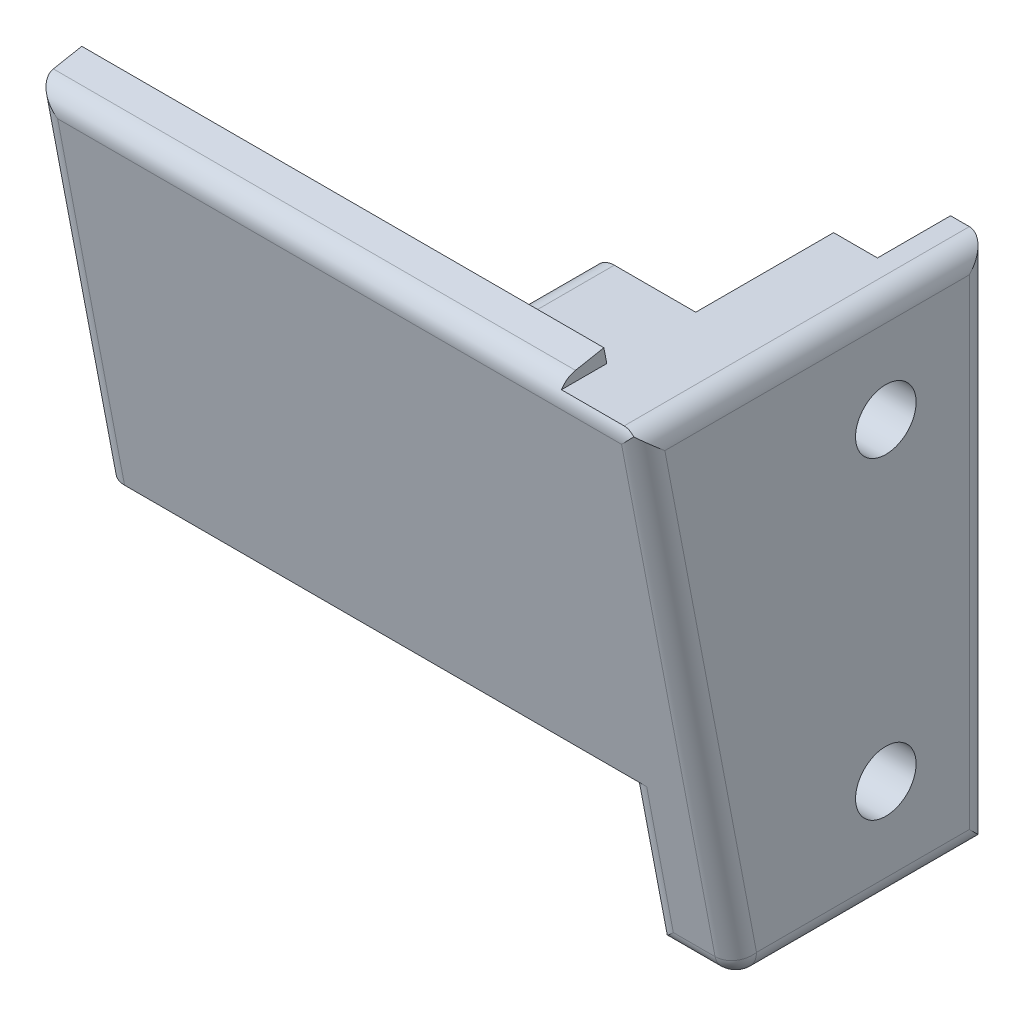
SolidWorks part; units mm, degrees
ref_plane "前视基准面" through (0, 0, 0) normal (0, 0, 1) x (1, 0, 0)
ref_plane "上视基准面" through (0, 0, 0) normal (0, 1, 0) x (1, 0, 0)
ref_plane "右视基准面" through (0, 0, 0) normal (1, 0, 0) x (0, 0, -1)
other "Configuration Table"
sketch "草图1" plane through (0, 0, 0) normal (1, 0, 0) x (0, 0, -1)
  line L0 (0, 0) -> (-10, 0)
  line L1 (-10, 0) -> (-17.6299, 40)
  line L2 (-17.6299, 40) -> (-10, 41.4554)
  line L3 (-10, 41.4554) -> (-4, 10)
  line L4 (-4, 10) -> (0, 10)
  line L5 (0, 10) -> (0, 0)
  dimension "D1" = 10
  dimension "D2" = 4
  dimension "D3" = 10
  dimension "D4" = 6
  dimension "D5" = 40
extrude "凸台-拉伸1" add sketch "草图1" along normal blind 50
sketch "草图2" plane through (0, 0, 0) normal (0, -1, 0) x (1, 0, 0)
  line L4 (0, 10) -> (0, 0)
  line L5 (0, 0) -> (50, 0)
  line L6 (50, 0) -> (50, 10)
  line L7 (50, 10) -> (0, 10)
  line L8 (0, 10) -> (0, 0)
  line L9 (0, 0) -> (50, 0)
  line L10 (50, 0) -> (50, 10)
  line L11 (50, 10) -> (0, 10)
  dimension "D1" = 0
extrude "凸台-拉伸2" add sketch "草图2" along normal blind 10
sketch "草图3" plane through (0, 0, 0) normal (-1, 0, 0) x (0, 0, 1)
  line L1 (0, 10) -> (10, 10)
  line L2 (0, 10) -> (0, -10)
  line L3 (0, -10) -> (10, -10)
  line L4 (10, 10) -> (10, -10)
extrude "凸台-拉伸3" add sketch "草图3" along normal blind 20
sketch "草图4" plane through (0, 10, 0) normal (0, 1, 0) x (1, 0, 0)
  line L1 (-20, 0) -> (0, 0)
  line L2 (-20, 0) -> (-20, -10)
  line L3 (-20, -10) -> (0, -10)
  line L4 (0, 0) -> (0, -10)
extrude "凸台-拉伸4" add sketch "草图4" along normal blind 30
sketch "草图5" plane through (50, 0, 0) normal (1, 0, 0) x (0, 0, -1)
  line L0 (-10, 10.004) -> (-11.9082, 10.004)
  line L1 (-17.6299, 40) -> (-10, 0) construction
  line L2 (-11.9082, 10.004) -> (-10, 0)
  line L3 (-10, 0) -> (-10, 10.004)
extrude "切除-拉伸1" cut sketch "草图5" against normal up to surface (50 mm away) up to face at (0, 32.2911, 11.4705)
chamfer "倒角1" distance 2 angle 45 1 edges at (25, 10.004, 10)
sketch "草图9" plane through (0, 0, 10) normal (0, 0, 1) x (1, 0, 0)
  line L0 (-20, 40) -> (-10, 40) construction
  line L1 (-20, 40) -> (0, 40) construction
  line L2 (-10, 40) -> (-10, 30) construction
  line L3 (50, -10) -> (50, 0) construction
  line L4 (50, -10) -> (50, 8.004) construction
  line L5 (50, 0) -> (-10, 0) construction
  line L6 (-20, -10) -> (-20, 40) construction
  circle A0 centre (-10, 30) radius 1.5
  circle A1 centre (-10, 0) radius 1.5
  dimension "D3" = 3
  dimension "D5" = 3
  dimension "D4" = 10
  dimension "D1" = 10
  dimension "D2" = 10
extrude "切除-拉伸2" cut sketch "草图9" against normal through all
sketch "草图12" plane through (0, 0, 10) normal (0, 0, 1) x (1, 0, 0)
  line L8 (0, 40) -> (-20, 40)
  line L9 (50, -10) -> (50, 8.004)
  line L10 (50, 8.004) -> (0, 8.004)
  line L11 (0, 8.004) -> (0, 40)
  line L15 (50, -10) -> (50, 8.004)
  line L16 (50, 8.004) -> (0, 8.004)
  line L17 (0, 8.004) -> (0, 40)
  line L19 (0, 40) -> (-20, 40)
  line L20 (-20, 40) -> (-20, -10)
  line L21 (-20, 40) -> (-20, -10)
  line L22 (-20, -10) -> (50, -10)
  line L23 (-20, -10) -> (50, -10)
  dimension "D1" = 0
extrude "切除-拉伸4" cut sketch "草图12" against normal blind 6
sketch "草图13" plane through (0, 8.004, 0) normal (0, -1, 0) x (1, 0, 0)
  line L0 (50, 4) -> (0, 4) construction
  line L1 (0, 10) -> (4, 10)
  line L2 (0, 10) -> (0, 4)
  line L3 (0, 4) -> (4, 4)
  line L4 (4, 10) -> (4, 4)
  line L6 (50, 10) -> (46, 10)
  line L7 (50, 10) -> (50, 4)
  line L8 (50, 4) -> (46, 4)
  line L9 (46, 10) -> (46, 4)
  dimension "D1" = 4
  dimension "D2" = 4
extrude "凸台-拉伸12" add sketch "草图13" along normal up to surface (18.004 mm away) up to face at (15, -10, 2)
sketch "草图15" plane through (0, 0, 0) normal (0, 0, -1) x (-1, 0, 0)
  line L0 (-25, 10) -> (-25, 20.01) construction
  line L1 (0, 40) -> (20, 40) construction
  line L2 (0, 40) -> (0, -10) construction
  line L3 (0, -10) -> (20, -10) construction
  line L4 (20, 40) -> (20, -10) construction
  line L5 (-50, 10) -> (0, 10) construction
  line L6 (-50, -10) -> (-70, -10)
  line L7 (-70, 40) -> (-70, -10)
  line L8 (-50, 40) -> (-70, 40)
  line L9 (-50, 40) -> (-50, -10)
  circle A0 centre (10, 30) radius 1.5 construction
  circle A1 centre (-60, 30) radius 1.5
extrude "凸台-拉伸14" add sketch "草图15" against normal up to surface (4 mm away) up to face at (-8.5, 30, 4)
sketch "草图16" plane through (0, 0, 4) normal (0, 0, 1) x (1, 0, 0)
  line L5 (-20, -10) -> (0, -10)
  line L6 (0, -10) -> (0, 10)
  line L7 (0, 10) -> (0, 40)
  line L8 (0, 40) -> (-20, 40)
  line L9 (-20, 40) -> (-20, -10)
  line L10 (-20, -10) -> (0, -10)
  line L11 (0, -10) -> (0, 10)
  line L12 (0, 10) -> (0, 40)
  line L13 (0, 40) -> (-20, 40)
  line L14 (-20, 40) -> (-20, -10)
  dimension "D1" = 0
extrude "切除-拉伸5" cut sketch "草图16" against normal up to surface (4 mm away) up to face at (-8.5, 30, 0)
sketch "草图17" plane through (0, 0, 4) normal (0, 0, 1) x (1, 0, 0)
  line L1 (50, 10) -> (70, 10)
  line L2 (50, 10) -> (50, -10)
  line L3 (50, -10) -> (70, -10)
  line L4 (70, 10) -> (70, -10)
extrude "凸台-拉伸15" add sketch "草图17" along normal up to surface (6 mm away) up to face at (48, -0.998, 10)
sketch "草图18" plane through (0, 10, 0) normal (0, 1, 0) x (1, 0, 0)
  line L1 (0, 0) -> (50, 0)
  line L2 (0, 0) -> (0, -4)
  line L3 (0, -4) -> (50, -4)
  line L4 (50, 0) -> (50, -4)
extrude "切除-拉伸6" cut sketch "草图18" against normal up to surface (20 mm away) up to face at (30, -10, 6)
sketch "草图19" plane through (0, -10, 0) normal (0, -1, 0) x (1, 0, 0)
  line L1 (50, 6) -> (46, 6)
  line L2 (50, 6) -> (50, 10)
  line L3 (50, 10) -> (46, 10)
  line L4 (46, 6) -> (46, 10)
  line L5 (4, 6) -> (0, 6)
  line L6 (4, 6) -> (4, 10)
  line L7 (4, 10) -> (0, 10)
  line L8 (0, 6) -> (0, 10)
extrude "切除-拉伸9" cut sketch "草图19" against normal up to surface (18.004 mm away) up to face at (25, 8.004, 7)
sketch "草图20" plane through (0, 0, 4) normal (0, 0, 1) x (1, 0, 0)
  line L0 (50, 10) -> (70, 10) construction
  line L1 (50, 40) -> (55, 40)
  line L2 (50, 40) -> (50, 10)
  line L3 (50, 10) -> (55, 10)
  line L4 (55, 40) -> (55, 10)
  dimension "D1" = 5
extrude "凸台-拉伸16" add sketch "草图20" along normal up to surface (13.6299 mm away)
sketch "草图21" plane through (0, 8.004, 0) normal (0, -1, 0) x (1, 0, 0)
  line L4 (50, 10) -> (0, 10)
  line L5 (0, 10) -> (0, 6)
  line L6 (4, 4) -> (46, 4)
  line L8 (50, 10) -> (0, 10)
  line L10 (4, 4) -> (46, 4)
  line L12 (0, 10) -> (0, 6)
  line L14 (50, 6) -> (50, 10)
  line L15 (50, 6) -> (50, 10)
  line L20 (4, 6) -> (4, 4)
  line L21 (4, 6) -> (4, 4)
  line L22 (46, 4) -> (46, 6)
  line L23 (46, 4) -> (46, 6)
  line L24 (46, 6) -> (50, 6)
  line L25 (46, 6) -> (50, 6)
  line L26 (0, 6) -> (4, 6)
  line L27 (0, 6) -> (4, 6)
  dimension "D1" = 0
extrude "凸台-拉伸17" add sketch "草图21" along normal up to surface (18.004 mm away) up to face at (54, -10, 5)
sketch "草图22" plane through (0, 0, 10) normal (0, 0, 1) x (1, 0, 0)
  line L0 (70, 10) -> (70, -10) construction
  line L1 (10, 5) -> (70, 5)
  line L2 (10, 5) -> (10, -5)
  line L3 (10, -5) -> (70, -5)
  line L4 (70, 5) -> (70, -5)
  line L5 (55, 10) -> (70, 10) construction
  line L6 (70, -10) -> (0, -10) construction
  line L8 (0, -10) -> (0, 8.004) construction
  dimension "D1" = 5
  dimension "D2" = 5
  dimension "D3" = 10
extrude "切除-拉伸10" cut sketch "草图22" against normal up to surface (6 mm away) up to face at (61.5, 30, 4)
sketch "草图23" plane through (0, 0, 0) normal (0, 0, -1) x (-1, 0, 0)
  line L0 (-60, 30) -> (-60, 0) construction
  circle A0 centre (-60, 0) radius 1.5
  dimension "D1" = 3
extrude "切除-拉伸11" cut sketch "草图23" against normal up to surface (4 mm away) up to face at (60, 0, 4)
chamfer "倒角2" distance 1 angle 45 1 edges at (52.5, 10, 10)
sketch "草图24" plane through (0, 0, 4) normal (0, 0, 1) x (1, 0, 0)
  circle A0 centre (60, 30) radius 3
  circle A1 centre (60, 0) radius 3
  dimension "D1" = 6
  dimension "D2" = 6
extrude "切除-拉伸12" cut sketch "草图24" against normal blind 2
sketch "草图25" plane through (0, 0, 10) normal (0, 0, 1) x (1, 0, 0)
  line L1 (55, 40) -> (70, 40)
  line L2 (55, 40) -> (55, -10)
  line L3 (55, -10) -> (70, -10)
  line L4 (70, 40) -> (70, -10)
extrude "切除-拉伸13" cut sketch "草图25" against normal up to surface (10 mm away) up to face at (58.5, 0, 0)
sketch "草图26" plane through (0, 0, 0) normal (0, 0, -1) x (-1, 0, 0)
  line L4 (-50, 40) -> (-55, 40)
  line L5 (-55, 40) -> (-55, -10)
  line L6 (-55, -10) -> (-50, -10)
  line L7 (-50, -10) -> (-50, 40)
  line L8 (-50, 40) -> (-55, 40)
  line L9 (-55, 40) -> (-55, -10)
  line L10 (-55, -10) -> (-50, -10)
  line L11 (-50, -10) -> (-50, 40)
  dimension "D1" = 0
extrude "凸台-拉伸18" add sketch "草图26" along normal blind 19
sketch "草图27" plane through (50, 0, 0) normal (-1, 0, 0) x (0, 0, 1)
  line L0 (4, -10) -> (-19, -10) construction
  line L1 (-19, 40) -> (-12, 40)
  line L2 (-19, 40) -> (-19, -10)
  line L3 (-19, -10) -> (-12, -10)
  line L4 (-12, 40) -> (-12, -10)
  dimension "D1" = 7
extrude "切除-拉伸14" cut sketch "草图27" against normal blind 4.2
sketch "草图28" plane through (55, 0, 0) normal (1, 0, 0) x (0, 0, -1)
  line L10 (-10, -10) -> (19, -10)
  line L11 (19, -10) -> (19, 40)
  line L12 (19, 40) -> (-17.6299, 40)
  line L13 (-17.6299, 40) -> (-11.9075, 10)
  line L14 (-11.9075, 10) -> (-11, 10)
  line L15 (-10, 9) -> (-10, 5)
  line L16 (-10, 5) -> (-4, 5)
  line L17 (-4, 5) -> (-4, -5)
  line L18 (-4, -5) -> (-10, -5)
  line L19 (-10, -5) -> (-10, -10)
  line L20 (-10, -10) -> (19, -10)
  line L21 (19, -10) -> (19, 40)
  line L22 (19, 40) -> (-17.6299, 40)
  line L23 (-17.6299, 40) -> (-11.9075, 10)
  line L25 (-10, 9) -> (-10, 5)
  line L26 (-10, 5) -> (-4, 5)
  line L27 (-4, 5) -> (-4, -5)
  line L28 (-4, -5) -> (-10, -5)
  line L29 (-10, -5) -> (-10, -10)
  line L30 (-11.9075, 10) -> (-11, 10)
  line L32 (-11, 10) -> (-10, 9)
  line L33 (-11, 10) -> (-10, 9)
  dimension "D1" = 0
extrude "凸台-拉伸19" add sketch "草图28" along normal blind 3
sketch "草图29" plane through (58, 0, 0) normal (1, 0, 0) x (0, 0, -1)
  line L0 (19, 40) -> (9, 40) construction
  line L1 (19, 40) -> (-17.6299, 40) construction
  line L2 (9, 40) -> (9, 30) construction
  line L3 (9, 30) -> (9, 0) construction
  circle A0 centre (9, 30) radius 1.5
  circle A1 centre (9, 0) radius 1.5
  dimension "D4" = 3
  dimension "D5" = 3
  dimension "D1" = 10
  dimension "D2" = 10
  dimension "D3" = 30
extrude "切除-拉伸15" cut sketch "草图29" against normal blind 13
sketch "草图30" plane through (58, 0, 0) normal (1, 0, 0) x (0, 0, -1)
  circle A0 centre (9, 30) radius 2.9
  circle A1 centre (9, 0) radius 2.9
  dimension "D1" = 5.8
  dimension "D2" = 5.8
extrude "切除-拉伸16" cut sketch "草图30" against normal offset from surface (6 mm away) 2 up to face at (50, 40.4851, 12.4508)
sketch "草图31" plane through (10, 0, 0) normal (1, 0, 0) x (0, 0, -1)
  line L4 (-4, 5) -> (-10, 5)
  line L5 (-10, 5) -> (-10, -5)
  line L6 (-10, -5) -> (-4, -5)
  line L7 (-4, -5) -> (-4, 5)
  line L8 (-4, 5) -> (-10, 5)
  line L9 (-10, 5) -> (-10, -5)
  line L10 (-10, -5) -> (-4, -5)
  line L11 (-4, -5) -> (-4, 5)
  dimension "D1" = 0
extrude "切除-拉伸17" cut sketch "草图31" against normal up to surface (10 mm away) up to face at (0, 12.7643, 9.6452)
sketch "草图32" plane through (0, 0, 4) normal (0, 0, 1) x (1, 0, 0)
  line L4 (50, -5) -> (58, -5)
  line L5 (58, -5) -> (58, 5)
  line L6 (58, 5) -> (50, 5)
  line L7 (50, 5) -> (50, -5)
  line L8 (50, -5) -> (58, -5)
  line L9 (58, -5) -> (58, 5)
  line L10 (58, 5) -> (50, 5)
  line L11 (50, 5) -> (50, -5)
  dimension "D1" = 0
extrude "凸台-拉伸20" add sketch "草图32" along normal up to surface (6 mm away) up to face at (36, 7.3347, 10)
sketch "草图33" plane through (0, 0, 10) normal (0, 0, 1) x (1, 0, 0)
  line L1 (50, -5) -> (0, -5)
  line L2 (50, -5) -> (50, -10)
  line L3 (50, -10) -> (0, -10)
  line L4 (0, -5) -> (0, -10)
extrude "切除-拉伸18" cut sketch "草图33" against normal up to surface (6 mm away) up to face at (25, 7.5, 4)
sketch "草图34" plane through (0, 40, 0) normal (0, 1, 0) x (1, 0, 0)
  line L0 (50, -9.7224) -> (50, 12) construction
  line L1 (50, -1.2) -> (40.2, -1.2)
  line L2 (50, -1.2) -> (50, -10)
  line L3 (50, -10) -> (40.2, -10)
  line L4 (40.2, -1.2) -> (40.2, -10)
  line L6 (54.2, 19) -> (58, 19) construction
  line L11 (50, -10) -> (0, -10) construction
  dimension "D1" = 20.2
  dimension "D2" = 9.8
extrude "凸台-拉伸21" add sketch "草图34" against normal up to surface (35 mm away) up to face at (25, 5, 7)
sketch "草图35" plane through (0, -1.8405, 9.6489) normal (0, -0.1874, 0.9823) x (1, 0, 0)
  line L7 (0, 42.5949) -> (0, 11.9426)
  line L8 (0, 11.9426) -> (50, 11.9426)
  line L9 (50, 11.9426) -> (50, 12.054)
  line L10 (50, 12.054) -> (58, 12.054)
  line L11 (58, 12.054) -> (58, 42.5949)
  line L12 (58, 42.5949) -> (50, 42.5949)
  line L13 (50, 42.5949) -> (0, 42.5949)
  line L14 (0, 42.5949) -> (0, 11.9426)
  line L15 (0, 11.9426) -> (50, 11.9426)
  line L16 (50, 11.9426) -> (50, 12.054)
  line L17 (50, 12.054) -> (58, 12.054)
  line L18 (58, 12.054) -> (58, 42.5949)
  line L19 (58, 42.5949) -> (50, 42.5949)
  line L20 (50, 42.5949) -> (0, 42.5949)
  dimension "D1" = 0
extrude "切除-拉伸19" cut sketch "草图35" against normal blind 3
sketch "草图36" plane through (0, 11.7311, 2.2377) normal (0, 0.9823, 0.1874) x (1, 0, 0)
  line L1 (0, -6.8229) -> (58, -6.8229)
  line L2 (0, -6.8229) -> (0, -11.6966)
  line L3 (0, -11.6966) -> (58, -11.6966)
  line L4 (58, -6.8229) -> (58, -11.6966)
extrude "切除-拉伸20" cut sketch "草图36" against normal blind 24
sketch "草图37" plane through (0, 11.8405, 2.2585) normal (0, 0.9823, 0.1874) x (1, 0, 0)
  line L4 (50, -9.8229) -> (58, -9.8229)
  line L5 (58, -9.8229) -> (58, -6.8229)
  line L6 (58, -6.8229) -> (50, -6.8229)
  line L7 (50, -6.8229) -> (50, -9.8229)
  line L8 (50, -9.8229) -> (58, -9.8229)
  line L9 (58, -9.8229) -> (58, -6.8229)
  line L10 (58, -6.8229) -> (50, -6.8229)
  line L11 (50, -6.8229) -> (50, -9.8229)
  dimension "D1" = 0
extrude "切除-拉伸21" cut sketch "草图37" against normal blind 24
fillet "圆角1" radius 2 2 edges at (40.2, 5, 2.6) (40.2, 40, 5.4612)
fillet "圆角2" radius 2 8 edges at (50, -2.5, 6.469) (54, -10, 5.0384) (58, 15, 9.8071) (58, 40, -2.2121) (58, -10, -6.9808) (58, 15, -19) (0, 22.7811, 11.2913) (25, 40.5621, 14.683)
fillet "圆角3" radius 5 1 edges at (20.1, 10, 4)
